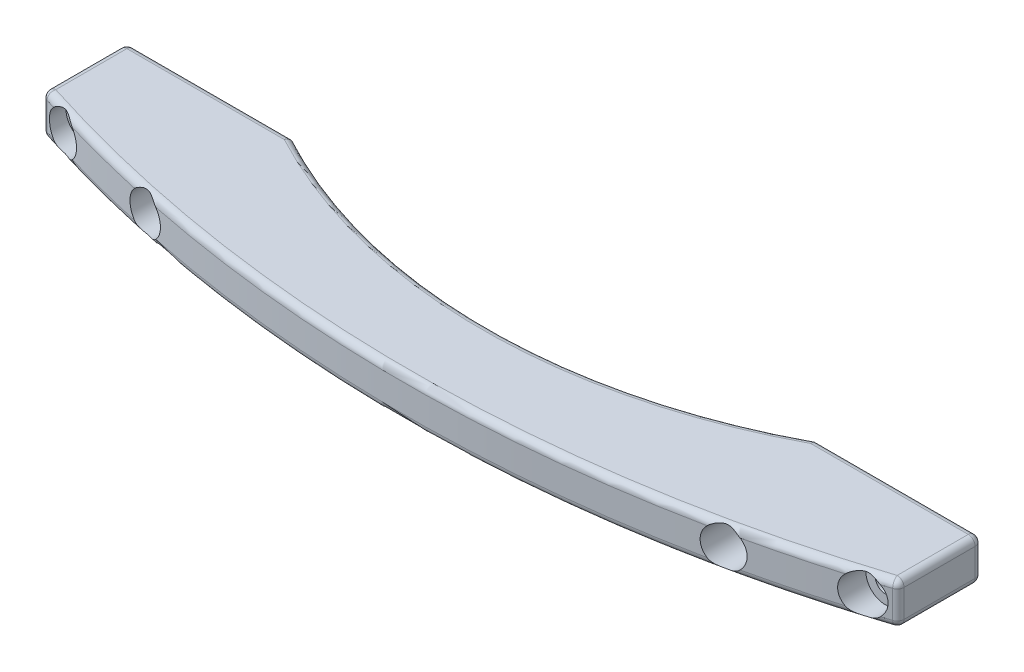
SolidWorks part; units mm, degrees
ref_plane "Front Plane" through (0, 0, 0) normal (0, 0, 1) x (1, 0, 0)
ref_plane "Top Plane" through (0, 0, 0) normal (0, 1, 0) x (1, 0, 0)
ref_plane "Right Plane" through (0, 0, 0) normal (1, 0, 0) x (0, 0, -1)
sketch "Sketch1" plane through (0, 0, 0) normal (0, 1, 0) x (1, 0, 0)
  line L0 (0, 0) -> (0, -19.05)
  line L1 (196.215, 0) -> (196.215, -19.05)
  line L2 (0, 0) -> (38.1, 0)
  line L3 (196.215, 0) -> (158.115, 0)
  arc A1 (0, -19.05) -> (196.215, -19.05) centre (98.1075, 282.9122) ccw
  arc A2 (38.1, 0) -> (158.115, 0) centre (98.1075, 111.929) ccw
  dimension "D6" = 127
  dimension "D7" = 317.5
  dimension "D1" = 196.215
  dimension "D2" = 38.1
  dimension "D3" = 38.1
  dimension "D4" = 19.05
  dimension "D5" = 19.05
extrude "Boss-Extrude1" add sketch "Sketch1" along normal blind 9.525
ref_plane "Plane1" through (98.1075, 0, 0) normal (1, 0, 0) x (0, 0, -1)
sketch "Sketch2" plane through (0, 0, 0) normal (0, 0, -1) x (-1, 0, 0)
  line L0 (-31.75, 4.7625) -> (-38.1, 4.7625) construction
  line L1 (-38.1, 9.525) -> (-38.1, 0) construction
  line L2 (-6.35, 4.7625) -> (0, 4.7625) construction
  line L3 (0, 9.525) -> (0, 0) construction
  circle A0 centre (-6.35, 4.7625) radius 2.286
  circle A1 centre (-31.75, 4.7625) radius 2.286
  dimension "D1" = 4.572
  dimension "D2" = 25.4
extrude "Cut-Extrude1" cut sketch "Sketch2" against normal through all
ref_plane "Plane2" through (98.1075, 0, 0) normal (-1, 0, 0) x (0, 0, 1)
ref_plane "Plane3" through (0, 0, 31.75) normal (0, 0, -1) x (-1, 0, 0)
sketch "Sketch3" plane through (0, 0, 31.75) normal (0, 0, -1) x (-1, 0, 0)
  circle A0 centre (-31.75, 4.7625) radius 4.445
  circle A1 centre (-6.35, 4.7625) radius 4.445
  dimension "D1" = 8.89
  dimension "D2" = 8.89
extrude "Cut-Extrude2" cut sketch "Sketch3" along normal blind 15.875
mirror "Mirror1" about plane through (98.1075, 0, 0) normal (-1, 0, 0) of "Cut-Extrude2", "Cut-Extrude1"
fillet "Fillet1" radius 1.5875 16 edges at (0, 4.7625, 0) (0, 4.7625, 19.05) (0, 0, 9.525) (98.1075, 0, 34.5878) (196.215, 0, 9.525) (177.165, 0, 0) (98.1075, 0, 15.071) (19.05, 0, 0) (98.1075, 9.525, 15.071) (177.165, 9.525, 0) (196.215, 9.525, 9.525) (98.1075, 9.525, 34.5878) (0, 9.525, 9.525) (19.05, 9.525, 0) (196.215, 4.7625, 0) (196.215, 4.7625, 19.05)
